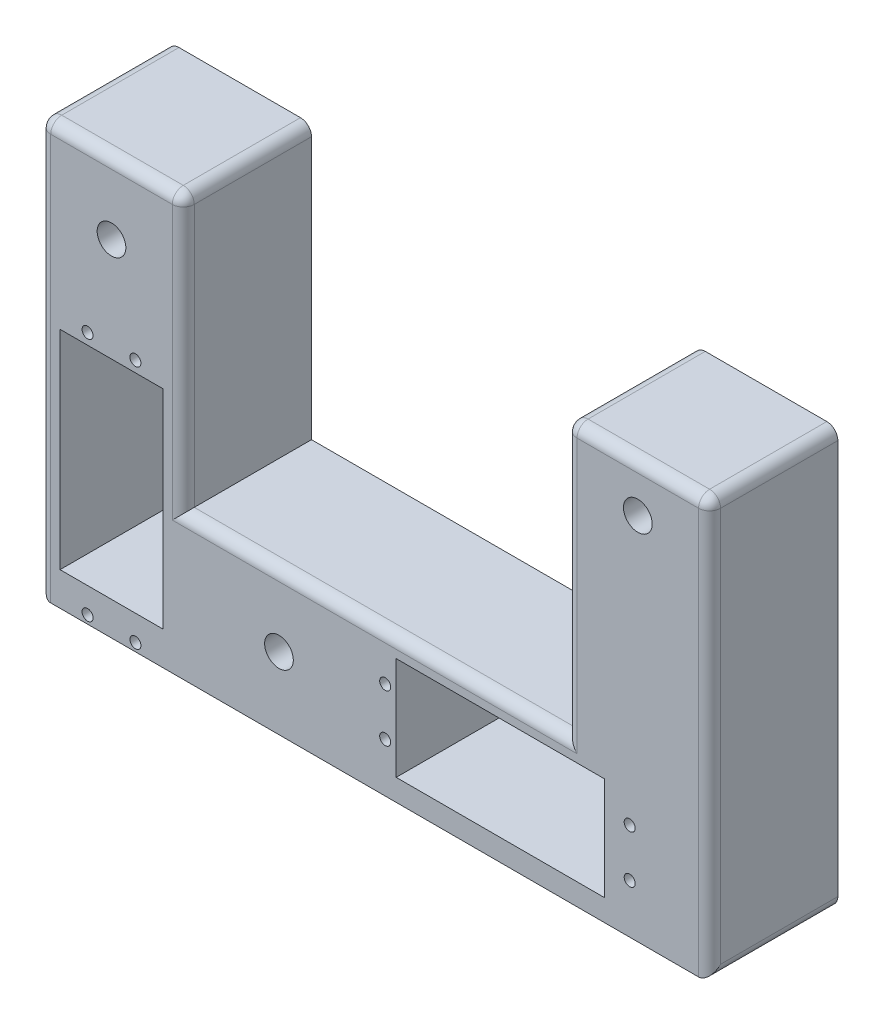
SolidWorks part; units mm, degrees
ref_plane "Front Plane" through (0, 0, 0) normal (0, 0, 1) x (1, 0, 0)
ref_plane "Top Plane" through (0, 0, 0) normal (0, 1, 0) x (1, 0, 0)
ref_plane "Right Plane" through (0, 0, 0) normal (1, 0, 0) x (0, 0, -1)
sketch "Sketch1" plane through (0, 0, 0) normal (0, 0, 1) x (1, 0, 0)
  line L1 (86.9545, 12.865) -> (116.9545, 12.865)
  line L2 (86.9545, 42.865) -> (86.9545, 100)
  line L3 (86.9545, 100) -> (116.9545, 100)
  line L4 (116.9545, 12.865) -> (116.9545, 100)
  line L5 (6.9545, 100) -> (-23.0455, 100)
  line L6 (6.9545, 100) -> (6.9545, 42.865)
  line L7 (6.9545, 12.865) -> (-23.0455, 12.865)
  line L8 (-23.0455, 100) -> (-23.0455, 12.865)
  line L9 (6.9545, 12.865) -> (86.9545, 12.865)
  line L11 (6.9545, 42.865) -> (86.9545, 42.865)
  dimension "D1" = 80
  dimension "D2" = 30
  dimension "D3" = 30
extrude "Boss-Extrude1" add sketch "Sketch1" along normal blind 26.8 contours L6 L11 L2 L3 L4 L1 L9 L7 L8 L5
sketch "Sketch2" plane through (0, 0, 26.8) normal (0, 0, 1) x (1, 0, 0)
  line L0 (46.9545, 12.865) -> (46.9545, 163.1977) construction
  line L1 (116.9545, 12.865) -> (-23.0455, 12.865) construction
  line L2 (-23.0455, 67.865) -> (116.9545, 67.865) construction
  line L3 (-23.0455, 100) -> (-23.0455, 12.865) construction
  line L4 (116.9545, 12.865) -> (116.9545, 100) construction
  line L5 (-8.0455, 100) -> (-8.0455, 12.865) construction
  line L6 (-18.7955, 63.365) -> (2.7045, 63.365)
  line L7 (-18.7955, 63.365) -> (-18.7955, 19.865)
  line L8 (-18.7955, 19.865) -> (2.7045, 19.865)
  line L9 (2.7045, 63.365) -> (2.7045, 19.865)
  line L10 (51.4545, 38.8955) -> (94.9545, 38.8955)
  line L11 (51.4545, 38.8955) -> (51.4545, 17.3955)
  line L12 (51.4545, 17.3955) -> (94.9545, 17.3955)
  line L13 (94.9545, 38.8955) -> (94.9545, 17.3955)
  line L14 (6.9545, 100) -> (-23.0455, 100) construction
  line L15 (-23.0455, 28.1455) -> (116.9545, 28.1455) construction
  dimension "D1" = 55
  dimension "D2" = 48
  dimension "D3" = 21.5
  dimension "D4" = 43.5
  dimension "D5" = 21.5
  dimension "D6" = 43.5
  dimension "D7" = 48
  dimension "D8" = 10.75
  dimension "D9" = 10.75
extrude "Cut-Extrude1" cut sketch "Sketch2" against normal through all
sketch "Sketch3" plane through (0, 0, 26.8) normal (0, 0, 1) x (1, 0, 0)
  line L0 (-18.7955, 19.865) -> (2.7045, 19.865) construction
  line L1 (-8.0455, 63.365) -> (-8.0455, -3.066) construction
  line L2 (2.7045, 63.365) -> (-18.7955, 63.365) construction
  circle A0 centre (-13.0455, 14.565) radius 1.15
  circle A1 centre (-3.0455, 14.565) radius 1.15
  circle A2 centre (-13.0455, 65.665) radius 1.15
  circle A3 centre (-3.0455, 65.665) radius 1.15
  dimension "D3" = 2.3
  dimension "D4" = 2.3
  dimension "D7" = 2.3
  dimension "D1" = 5.3
  dimension "D2" = 5.3
  dimension "D5" = 10
  dimension "D6" = 5
  dimension "D8" = 2.3
  dimension "D9" = 5
extrude "Boss-Extrude2" add sketch "Sketch3" against normal through all
extrude "Cut-Extrude2" cut sketch "Sketch3<2>" against normal through all
sketch "Sketch3<2>" plane through (0, 0, 26.8) normal (0, 0, 1) x (1, 0, 0) same geometry as "Sketch3"
sketch "Sketch4" plane through (0, 0, 26.8) normal (0, 0, 1) x (1, 0, 0)
  line L0 (51.4545, 28.1455) -> (128.9839, 28.1455) construction
  line L1 (51.4545, 38.8955) -> (51.4545, 17.3955) construction
  line L2 (94.9545, 17.3955) -> (94.9545, 38.8955) construction
  circle A0 centre (100.2545, 23.1455) radius 1.15
  circle A1 centre (100.2545, 33.1455) radius 1.15
  circle A2 centre (49.1545, 23.1455) radius 1.15
  circle A3 centre (49.1545, 33.1455) radius 1.15
  dimension "D1" = 2.3
  dimension "D4" = 2.3
  dimension "D2" = 5.3
  dimension "D3" = 5
  dimension "D5" = 2.3
  dimension "D6" = 5
extrude "Cut-Extrude3" cut sketch "Sketch4" against normal through all
fillet "Fillet1" radius 2.3 13 edges at (-23.0455, 12.865, 13.4) (-23.0455, 100, 13.4) (6.9545, 100, 13.4) (86.9545, 100, 13.4) (116.9545, 100, 13.4) (116.9545, 12.865, 13.4) (101.9545, 100, 26.8) (86.9545, 71.4325, 26.8) (116.9545, 56.4325, 26.8) (46.9545, 42.865, 26.8) (6.9545, 71.4325, 26.8) (-8.0455, 100, 26.8) (-23.0455, 56.4325, 26.8)
sketch "Sketch6" plane through (0, 0, 0) normal (0, 0, 1) x (1, 0, 0)
  line L6 (114.6545, 12.865) -> (-20.7455, 12.865) construction
  line L7 (-23.0455, 15.165) -> (-23.0455, 97.7) construction
  line L8 (89.2545, 100) -> (114.6545, 100) construction
  line L9 (116.9545, 97.7) -> (116.9545, 15.165) construction
  line L10 (-20.7455, 100) -> (4.6545, 100) construction
  line L11 (6.9545, 97.7) -> (6.9545, 42.865) construction
  circle A0 centre (101.9545, 90) radius 1.75
  circle A1 centre (-8.0455, 85) radius 1.75
  circle A2 centre (26.9545, 27.865) radius 1.75
  dimension "D1" = 3.5
  dimension "D2" = 3.5
  dimension "D7" = 3.5
  dimension "D3" = 15
  dimension "D4" = 50
  dimension "D5" = 10
  dimension "D6" = 15
  dimension "D8" = 15
  dimension "D9" = 15
extrude "Cut-Extrude4" cut sketch "Sketch6" along normal through all
sketch "Sketch7" plane through (0, 0, 26.8) normal (0, 0, 1) x (1, 0, 0)
  circle A0 centre (-8.0455, 85) radius 3
  circle A1 centre (26.9545, 27.865) radius 3
  circle A2 centre (101.9545, 90) radius 3
  dimension "D1" = 6
  dimension "D2" = 6
  dimension "D3" = 6
extrude "Cut-Extrude5" cut sketch "Sketch7" against normal blind 5
